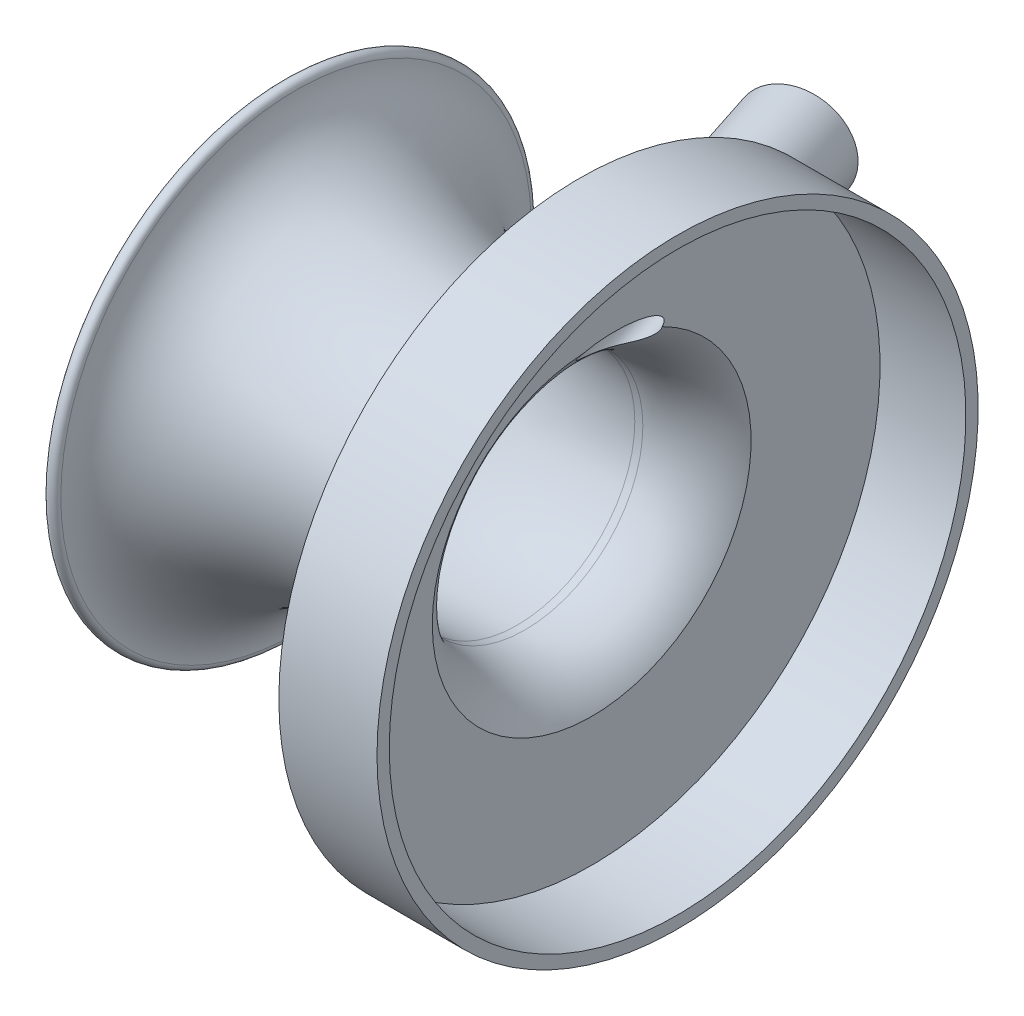
SolidWorks part; units mm, degrees
material "PVC 0.007 Plasticized"
ref_plane "Front Plane" through (0, 0, 0) normal (0, 0, 1) x (1, 0, 0)
ref_plane "Top Plane" through (0, 0, 0) normal (0, 1, 0) x (1, 0, 0)
ref_plane "Right Plane" through (0, 0, 0) normal (1, 0, 0) x (0, 0, -1)
sketch "Sketch1" plane through (0, 0, 0) normal (0, 0, 1) x (1, 0, 0)
  line L0 (-17.78, 33.4033) -> (-17.78, 60.0933)
  line L1 (-34.3222, 33.4033) -> (-9.5791, 33.4033) construction
  line L3 (-34.3222, 0.4033) -> (53.9483, 0.4033) construction
  line L11 (-33.2131, 24.7619) -> (-31.5799, 24.7915)
  line L12 (-17.78, 60.0933) -> (0, 60.0933)
  line L13 (-33.2365, 27.3019) -> (-31.68, 27.3301)
  line L14 (-20.32, 34.0999) -> (-20.32, 62.6333)
  line L15 (-20.32, 62.6333) -> (0, 62.6333)
  line L16 (0, 62.6333) -> (0, 60.0933)
  circle A4 centre (-32.5832, 41.7619) radius 17 construction
  arc A5 (-17.78, 33.4033) -> (-31.5799, 24.7915) centre (-32.5832, 41.7619) cw
  arc A6 (-20.32, 34.0999) -> (-31.68, 27.3301) centre (-32.5832, 41.7619) cw
  arc A7 (-81.5276, 49.1004) -> (-78.9876, 49.1015) centre (-80.2576, 49.101) cw
  ellipse E0 centre (-33.2232, 49.1205) end of major axis (-81.5276, 49.1004) minor radius 24.3586 (-81.5276, 49.1004) -> (-33.2131, 24.7619) ccw
  ellipse E1 centre (-33.2232, 49.1205) end of major axis (-81.5276, 49.1004) minor radius 24.3586 construction
  spline S0 degree 1 poles (-78.9876, 49.1015) (-33.2365, 27.3019) knots 0 0 1 1 construction
  spline S1 degree 3 poles (-78.9876, 49.1015) (-78.9874, 48.4651) (-78.8643, 47.2068) (-78.1154, 44.6473) (-76.1728, 41.3828) (-72.1247, 37.5428) (-66.4667, 34.0595) (-59.4331, 31.146) (-51.3175, 28.9592) (-42.4745, 27.6059) (-36.296, 27.3013) (-33.2365, 27.3019) knots 3.141593 3.141593 3.141593 3.141593 3.239738 3.337883 3.534173 3.730463 3.926753 4.123043 4.319333 4.515623 4.711913 4.711913 4.711913 4.711913
  dimension "D3" = 24.3586
  dimension "D1" = 33.0001
  dimension "D2" = 15.4432
  dimension "D4" = 48.3044
  dimension "D5" = 59.69
  dimension "D10" = 34
  dimension "D11" = 17
  dimension "D12" = 31.5799
  dimension "D9" = 1.27
  dimension "D6" = 17.78
  dimension "D8" = 24.3586
  dimension "D7" = 2.54
  dimension "D13" = 31.68
  dimension "D14" = 34.3222
  dimension "D15" = 0.4033
revolve "Revolve1" add sketch "Sketch1" angle 360 about L3
ref_axis "Axis1" through (0, 65.659, 0) along (0, -1, 0)
ref_plane "Plane1" through (0, 0, 0) normal (-0.309, 0, -0.9511) x (0, -1, 0)
ref_plane "Plane2" through (-13.3434, 0, -41.0666) normal (-0.309, 0, -0.9511) x (0, -1, 0)
sketch "Sketch2" plane through (-13.3434, 0, -41.0666) normal (-0.309, 0, -0.9511) x (0, -1, 0)
  line L0 (-33.0001, 18.6255) -> (-26.9006, 18.6255) construction
  circle A0 centre (-30.8893, 15.4505) radius 3.175
  circle A1 centre (-30.8893, 15.4505) radius 10.16
  circle A2 centre (-30.8893, 15.4505) radius 5.5562
  ellipse E0 centre (0, 18.6255) end of major axis (-33.0001, 18.6255) minor radius 9.0224 construction
  dimension "D1" = 6.35
  dimension "D2" = 20.32
  dimension "D3" = 11.1125
  dimension "D4" = 0
extrude "Boss-Extrude1" add sketch "Sketch2" against normal up to next separate body contours A2 A0 region at (-28.0376, 36.2884, -36.2922)
extrude "Cut-Extrude1" cut sketch "Sketch2<3>" along direction (-0.309, 0, -0.9511) on the side against the normal blind 40.64 and the other way through all contours A0 region at (-28.0376, 30.8893, -36.2922)
sketch "Sketch2<3>" plane through (-13.3434, 0, -41.0666) normal (-0.309, 0, -0.9511) x (0, -1, 0) same geometry as "Sketch2"
extrude "Boss-Extrude3" add sketch "Sketch2<4>" against normal blind 1.016 and the other way blind 25.4 contours A1 A2 region at (-28.0376, 40.7619, -36.2922)
sketch "Sketch2<4>" plane through (-13.3434, 0, -41.0666) normal (-0.309, 0, -0.9511) x (0, -1, 0) same geometry as "Sketch2"
